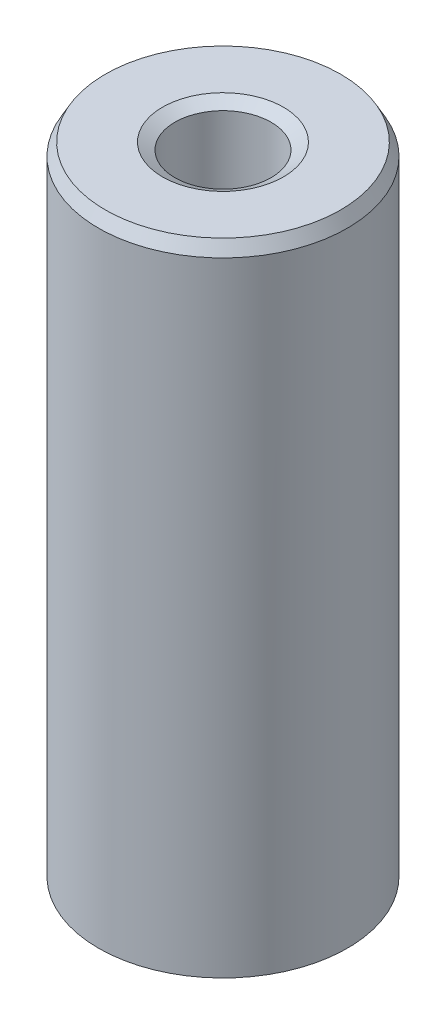
SolidWorks part; units mm, degrees
ref_plane "Front Plane" through (0, 0, 0) normal (0, 0, 1) x (1, 0, 0)
ref_plane "Top Plane" through (0, 0, 0) normal (0, 1, 0) x (1, 0, 0)
ref_plane "Right Plane" through (0, 0, 0) normal (1, 0, 0) x (0, 0, -1)
sketch "Sketch1" plane through (0, 0, 0) normal (0, 1, 0) x (1, 0, 0)
  circle A0 centre (0, 0) radius 7.5
  dimension "SLEEVE_OD" = 15
extrude "Boss-Extrude1" add sketch "Sketch1" along normal blind 38.7266
sketch "Sketch2" plane through (0, 0, 0) normal (0, 1, 0) x (1, 0, 0)
  circle A0 centre (0, 0) radius 2.8986
  dimension "BORE_D" = 5.7972
extrude "Cut-Extrude1" cut sketch "Sketch2" along normal through all
chamfer "Chamfer1" distance 0.7448 angle 28.959 4 edges at (0, 38.7266, 2.8986) (0, 0, 2.8986) (0, 0, 7.5) (0, 38.7266, 7.5) first distance on face at (0, 38.7266, 2.8986) first distance on face at (0, 0, 2.8986) first distance on face at (0, 38.7266, 7.5)
